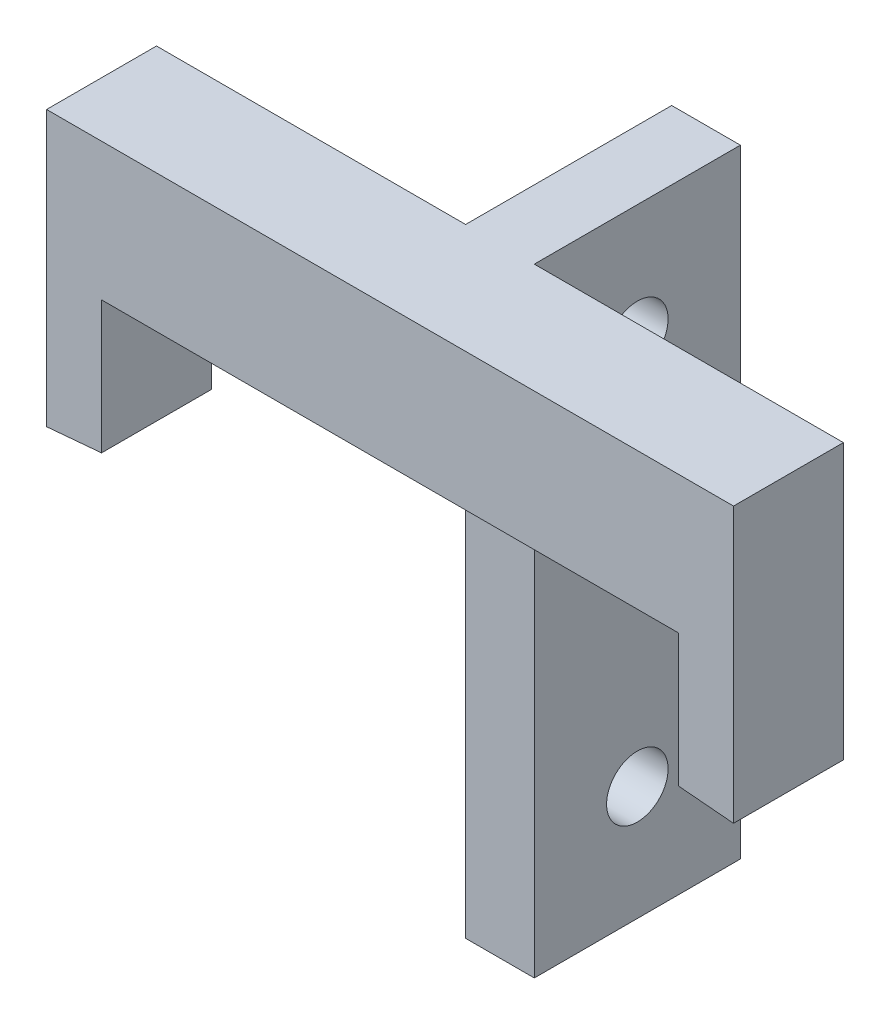
SolidWorks part; units mm, degrees
ref_plane "Front Plane" through (0, 0, 0) normal (0, 0, 1) x (1, 0, 0)
ref_plane "Top Plane" through (0, 0, 0) normal (0, 1, 0) x (1, 0, 0)
ref_plane "Right Plane" through (0, 0, 0) normal (1, 0, 0) x (0, 0, -1)
sketch "Sketch1" plane through (0, 0, 0) normal (0, 0, 1) x (1, 0, 0)
  line L4 (-1.5875, -14.2875) -> (1.5875, -14.2875)
  line L5 (-1.5875, -14.2875) -> (-1.5875, 14.2875)
  line L6 (-1.5875, 14.2875) -> (1.5875, 14.2875)
  line L7 (1.5875, -14.2875) -> (1.5875, 14.2875)
  line L8 (-1.5875, -14.2875) -> (1.5875, 14.2875) construction
  line L9 (-1.5875, 14.2875) -> (1.5875, -14.2875) construction
  point P0 (0, 0)
  dimension "D1" = 28.575
  dimension "D2" = 3.175
extrude "Boss-Extrude1" add sketch "Sketch1" along normal blind 9.525
sketch "Sketch4" plane through (1.5875, 0, 0) normal (1, 0, 0) x (0, 0, -1)
  line L0 (-9.525, 0) -> (0, 0) construction
  line L1 (-9.525, -14.2875) -> (-9.525, 14.2875) construction
  line L2 (-4.7625, 9.0043) -> (-4.7625, -9.0043) construction
  circle A0 centre (-4.7625, -9.0043) radius 1.4224
  circle A1 centre (-4.7625, 9.0043) radius 1.4224
  point P10 (-4.7625, 0)
  dimension "D2" = 2.8448
  dimension "D1" = 9.0043
extrude "Cut-Extrude1" cut sketch "Sketch4" against normal up to next
sketch "Sketch5" plane through (0, 0, 9.525) normal (0, 0, 1) x (1, 0, 0)
  line L0 (-1.5875, 14.2875) -> (1.5875, 14.2875) construction
  line L1 (15.875, 14.2875) -> (-15.875, 14.2875)
  line L2 (15.875, 14.2875) -> (15.875, 7.9375)
  line L3 (15.875, 7.9375) -> (-15.875, 7.9375)
  line L4 (-15.875, 14.2875) -> (-15.875, 7.9375)
  line L5 (15.875, 14.2875) -> (-15.875, 7.9375) construction
  line L6 (15.875, 7.9375) -> (-15.875, 14.2875) construction
  line L7 (15.875, 7.9375) -> (15.875, 1.5875)
  line L8 (15.875, 1.5875) -> (13.335, 1.8097)
  line L9 (13.335, 1.8097) -> (13.335, 7.9375)
  line L10 (13.335, 7.9375) -> (15.875, 7.9375)
  line L11 (0, 14.2875) -> (0, 7.9375) construction
  line L12 (-13.335, 7.9375) -> (-15.875, 7.9375)
  line L13 (-13.335, 1.8097) -> (-13.335, 7.9375)
  line L14 (-15.875, 1.5875) -> (-13.335, 1.8097)
  line L15 (-15.875, 7.9375) -> (-15.875, 1.5875)
  point P0 (0, 11.1125)
  line M5 (1.5875, -14.2875) -> (1.5875, 14.2875)
  line M6 (1.5875, 14.2875) -> (-1.5875, 14.2875)
  line M7 (-1.5875, 14.2875) -> (-1.5875, -14.2875)
  dimension "D1" = 6.35
  dimension "D2" = 31.75
  dimension "D3" = 2.54
  dimension "D4" = 6.35
  dimension "D5" = 85
extrude "Boss-Extrude3" add sketch "Sketch5" along normal blind 5.08 contours L1 L4 L3 M7 | L3 M5 M6 M7 | L3 L2 L1 M5 | L9 L8 L7 L3 | L3 L15 L14 L13 region at (8.7313, 11.1125, 9.525) region at (0, 11.1125, 9.525) region at (14.6125, 4.8177, 9.525) region at (-8.7312, 11.1125, 9.525) region at (-14.6125, 4.8177, 9.525)
